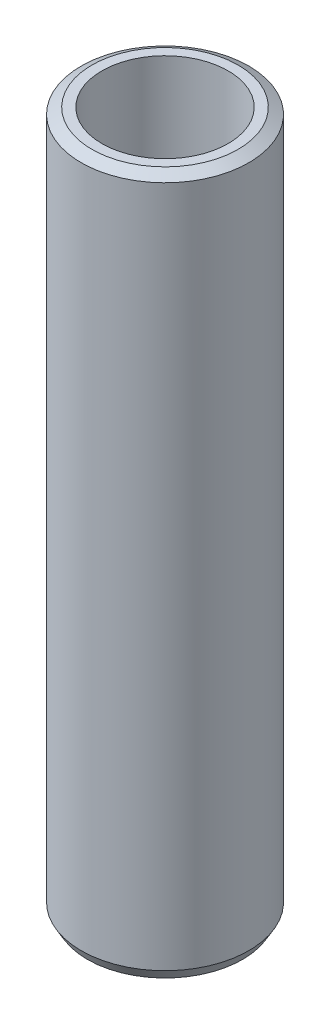
SolidWorks part; units mm, degrees
ref_plane "Front Plane" through (0, 0, 0) normal (0, 0, 1) x (1, 0, 0)
ref_plane "Top Plane" through (0, 0, 0) normal (0, 1, 0) x (1, 0, 0)
ref_plane "Right Plane" through (0, 0, 0) normal (1, 0, 0) x (0, 0, -1)
sketch "Sketch1" plane through (0, 0, 0) normal (0, 1, 0) x (1, 0, 0)
  circle A0 centre (0, 0) radius 57.5
  dimension "SHAFT_OD" = 115
extrude "Boss-Extrude1" add sketch "Sketch1" along normal blind 479.7423
sketch "Sketch2" plane through (0, 0, 0) normal (0, 1, 0) x (1, 0, 0)
  circle A0 centre (0, 0) radius 43.2859
  dimension "BORE_D" = 86.5718
extrude "Cut-Extrude1" cut sketch "Sketch2" along normal through all
chamfer "Chamfer1" distance 4.2482 angle 60 2 edges at (0, 479.7423, 57.5) (0, 0, 57.5) first distance on face at (0, 479.7423, 57.5) first distance on face at (0, 0, 43.2859)
